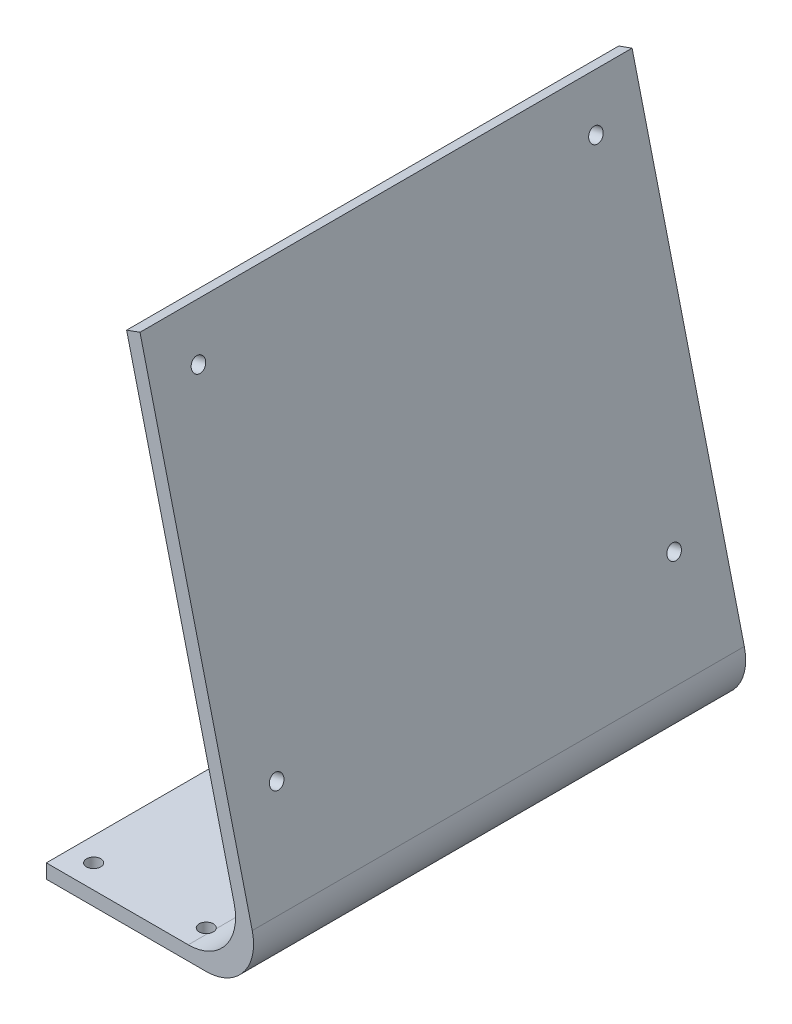
SolidWorks part; units mm, degrees
ref_plane "Front Plane" through (0, 0, 0) normal (0, 0, 1) x (1, 0, 0)
ref_plane "Top Plane" through (0, 0, 0) normal (0, 1, 0) x (1, 0, 0)
ref_plane "Right Plane" through (0, 0, 0) normal (1, 0, 0) x (0, 0, -1)
sketch "Sketch1" plane through (0, 0, 0) normal (0, 0, 1) x (1, 0, 0)
  line L0 (-50.53, 0) -> (-50.53, 3)
  line L1 (-50.53, 3) -> (-20.53, 3)
  line L2 (-50.53, 0) -> (-16.7319, 0)
  line L3 (-7.0146, 12.361) -> (-30.7379, 110)
  line L4 (-30.7379, 110) -> (-33.5595, 108.9811)
  line L5 (-33.5595, 108.9811) -> (-10.8127, 15.361)
  arc A0 (-10.8127, 15.361) -> (-20.53, 3) centre (-20.53, 13) cw
  arc A1 (-16.7319, 0) -> (-7.0146, 12.361) centre (-16.7319, 10) ccw
  dimension "D1" = 10
  dimension "D2" = 3
  dimension "D3" = 30
  dimension "D4" = 110
extrude "Boss-Extrude1" add sketch "Sketch1" along normal mid plane 104
sketch "Эскиз1" plane through (-3.7876, -0.9203, 0) normal (0.9717, 0.2361, 0) x (0, 0, -1)
  line L0 (-52, 114.1474) -> (52, 114.1474) construction
  line L1 (-47, 109.1474) -> (47, 109.1474) construction
  line L2 (-47, 109.1474) -> (-47, 29.1474) construction
  line L3 (-47, 29.1474) -> (47, 29.1474) construction
  line L4 (47, 109.1474) -> (47, 29.1474) construction
  line L5 (-47, 109.1474) -> (47, 29.1474) construction
  line L6 (-47, 29.1474) -> (47, 109.1474) construction
  line L7 (-52, 13.6677) -> (-52, 114.1474) construction
  point P0 (0, 69.1474)
  dimension "D1" = 80
  dimension "D2" = 94
  dimension "D3" = 5
  dimension "D4" = 5
sketch "Эскиз2" plane through (-3.7876, -0.9203, 0) normal (0.9717, 0.2361, 0) x (0, 0, -1)
  line L0 (-47, 109.1474) -> (-47, 29.1474) construction
  line L1 (-47, 109.1474) -> (47, 109.1474) construction
  line L2 (0, 69.1474) -> (0, 79.7671) construction
  line L3 (-47, 109.1474) -> (47, 29.1474) construction
  line L4 (0, 69.1474) -> (-10.9608, 69.1474) construction
  circle A0 centre (-42, 104.1474) radius 1.5
  circle A1 centre (42, 104.1474) radius 1.5
  circle A2 centre (42, 34.1474) radius 1.5
  circle A3 centre (-42, 34.1474) radius 1.5
  dimension "D1" = 5
  dimension "D2" = 5
extrude "Вырез-Вытянуть1" cut sketch "Эскиз2" against normal up to next
sketch "Sketch2" plane through (0, 0, 0) normal (0, -1, 0) x (1, 0, 0)
  line L0 (0, 0) -> (-74.033, 0) construction
  line L1 (-33.63, 33.8413) -> (-33.63, -3.8536) construction
  line L3 (-50.53, 52) -> (-50.53, -52) construction
  line L5 (-50.53, 52) -> (-16.7319, 52) construction
  circle A0 centre (-45.53, 47) radius 1.5
  circle A1 centre (-21.73, 47) radius 1.5
  circle A2 centre (-21.73, -47) radius 1.5
  circle A3 centre (-45.53, -47) radius 1.5
  dimension "D2" = 5
  dimension "D1" = 16.9
  dimension "D3" = 5
extrude "Cut-Extrude1" cut sketch "Sketch2" against normal up to next
